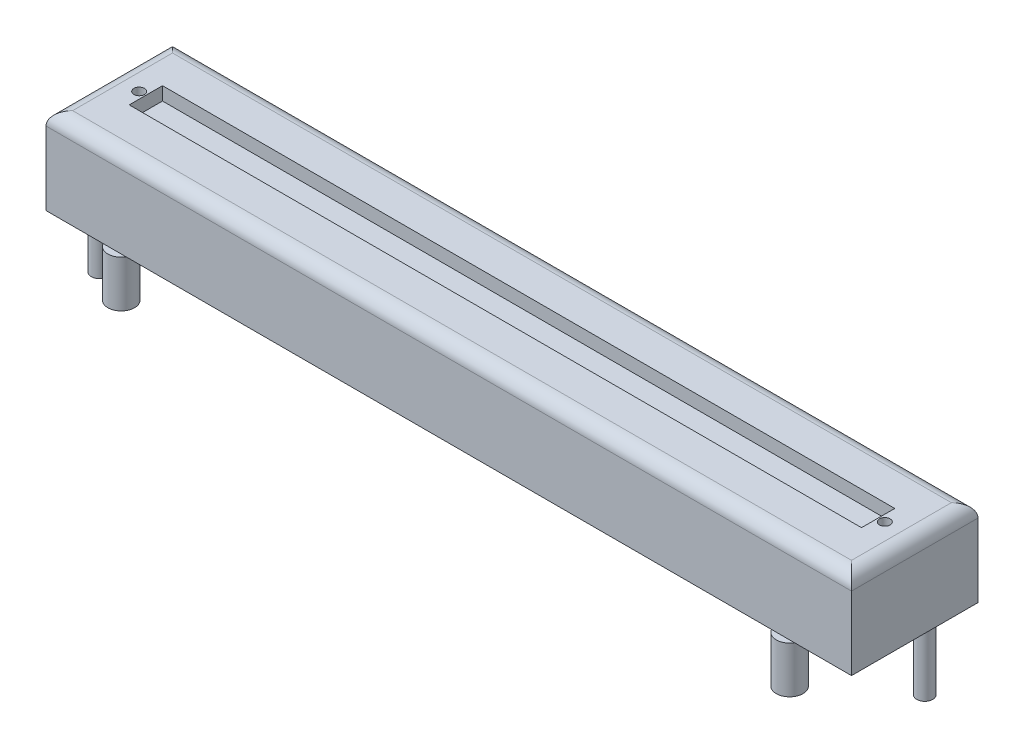
SolidWorks part; units mm, degrees
ref_plane "Front Plane" through (0, 0, 0) normal (0, 0, 1) x (1, 0, 0)
ref_plane "Top Plane" through (0, 0, 0) normal (0, 1, 0) x (1, 0, 0)
ref_plane "Right Plane" through (0, 0, 0) normal (1, 0, 0) x (0, 0, -1)
sketch "Sketch1" plane through (0, 0, 0) normal (0, 1, 0) x (1, 0, 0)
  line L0 (-30.25, 4.75) -> (30.25, -4.75) construction
  line L1 (-30.25, 4.75) -> (30.25, 4.75)
  line L2 (-30.25, 4.75) -> (-30.25, -4.75)
  line L3 (-30.25, -4.75) -> (30.25, -4.75)
  line L4 (30.25, 4.75) -> (30.25, -4.75)
  line L5 (-55, 0) -> (55, 0) construction
  line L6 (-28, 0) -> (28, 0) construction
  line L7 (0, -55) -> (0, 55) construction
  circle A0 centre (-28, 0) radius 0.4
  circle A1 centre (28, 0) radius 0.4
  dimension "D4" = 0.8
  dimension "D1" = 9.5
  dimension "D2" = 60.5
  dimension "D3" = 28
extrude "Boss-Extrude1" add sketch "Sketch1" along normal blind 6.5
sketch "Sketch2" plane through (0, 0, 0) normal (0, -1, 0) x (1, 0, 0)
  line L1 (-25.1, 4.25) -> (25.1, 4.25) construction
  line L2 (-23.9, -4.25) -> (23.9, -4.25) construction
  line L3 (0, -5.61) -> (0, 5.61) construction
  line L4 (0, 4.25) -> (0, -4.25) construction
  line L5 (6.325, 0) -> (-6.325, 0) construction
  line L6 (-29.25, 1.75) -> (29.25, 1.75) construction
  line L7 (-29.25, -1.75) -> (29.25, -1.75) construction
  line L8 (-29.25, 1.75) -> (29.25, -1.75) construction
  line L9 (29.25, -1.75) -> (29.25, 1.75) construction
  line L10 (-29.25, -1.75) -> (-29.25, 1.75) construction
  circle A1 centre (-25.1, 4.25) radius 1
  circle A2 centre (-23.9, -4.25) radius 1
  circle A3 centre (25.1, 4.25) radius 1
  circle A4 centre (23.9, -4.25) radius 1
  circle A5 centre (-29.25, 1.75) radius 0.6
  circle A6 centre (-29.25, -1.75) radius 0.6
  circle A8 centre (29.25, -1.75) radius 0.6
  point P3 (0, 0)
  point P18 (0, 4.25)
  point P19 (0, -4.25)
  dimension "D2" = 2
  dimension "D5" = 1.2
  dimension "D1" = 8.5
  dimension "D3" = 50.2
  dimension "D4" = 47.8
  dimension "D6" = 58.5
  dimension "D7" = 3.5
extrude "Boss-Extrude2" add sketch "Sketch2" along normal blind 3.5 contours A2 | A1 | A3 | A4
extrude "Boss-Extrude3" add sketch "Sketch2<3>" along normal blind 5 contours A6 | A5 | A8
sketch "Sketch2<3>" plane through (0, 0, 0) normal (0, -1, 0) x (1, 0, 0) same geometry as "Sketch2"
sketch "Sketch3" plane through (0, 0, 0) normal (0, -1, 0) x (1, 0, 0)
  line L0 (-27.4921, 1.2705) -> (27.7052, 1.2705) construction
  text T0 "2                                                                   2\r\n1                                                                   3" font "Century Gothic" height 2
sketch "Sketch4" plane through (0, 6.5, 0) normal (0, 1, 0) x (1, 0, 0)
  line L0 (-27.5, 1.25) -> (27.5, -1.25) construction
  line L1 (-27.5, 1.25) -> (27.5, 1.25)
  line L2 (-27.5, 1.25) -> (-27.5, -1.25)
  line L3 (-27.5, -1.25) -> (27.5, -1.25)
  line L4 (27.5, 1.25) -> (27.5, -1.25)
  dimension "D1" = 2.5
  dimension "D2" = 55
extrude "Cut-Extrude1" cut sketch "Sketch4" against normal blind 1
fillet "Fillet1" radius 1 4 edges at (30.25, 6.5, 0) (0, 6.5, -4.75) (-30.25, 6.5, 0) (0, 6.5, 4.75)
